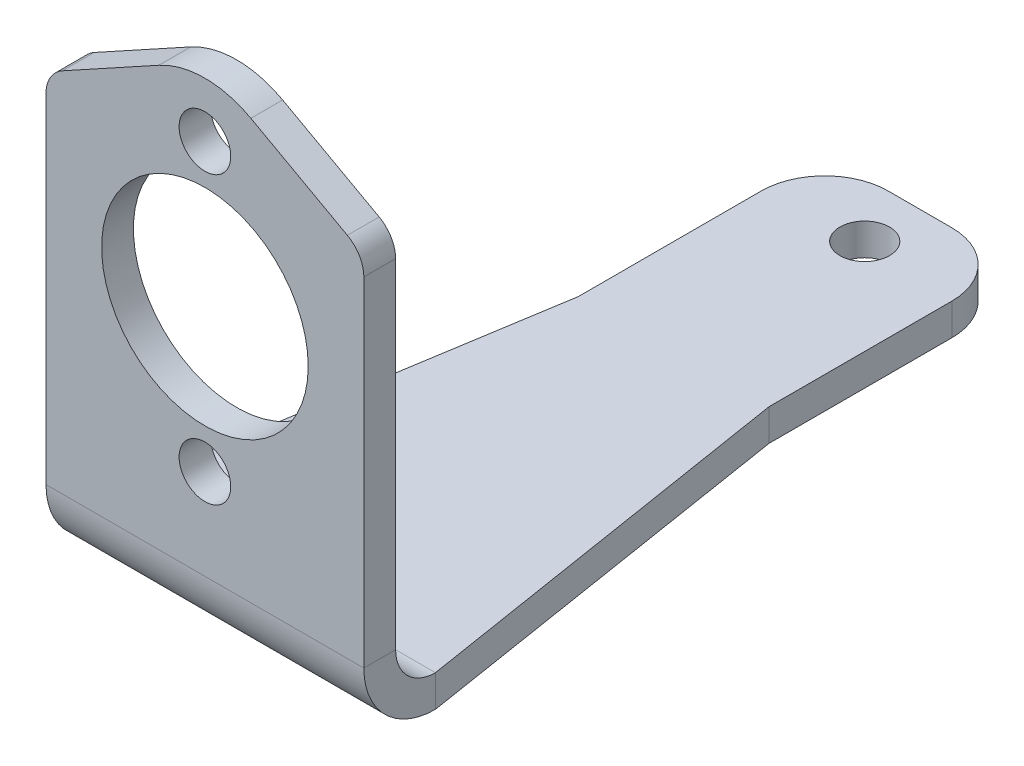
SolidWorks part; units mm, degrees
note: The reader was unsure of these and kept them because the rebuilt part matched: flange length of "Edge-Flange1".
material "Plain Carbon Steel"
ref_plane "Front" through (0, 0, 0) normal (0, 0, 1) x (1, 0, 0)
ref_plane "Top" through (0, 0, 0) normal (0, 1, 0) x (1, 0, 0)
ref_plane "Right" through (0, 0, 0) normal (1, 0, 0) x (0, 0, -1)
sketch "Sketch1" plane through (0, 0, 0) normal (0, 0, 1) x (1, 0, 0)
  line L0 (0, 85.725) -> (31.75, 103.1875)
  line L1 (0, 0) -> (63.5, 0)
  line L2 (0, 0) -> (0, 85.725)
  line L4 (63.5, 0) -> (63.5, 85.725)
  line L5 (31.75, 103.1875) -> (63.5, 85.725)
  circle A0 centre (31.75, 60.96) radius 20.6375
  circle A1 centre (31.75, 89.535) radius 5.1594
  circle A2 centre (31.75, 32.385) radius 5.1594
  point P7 (31.75, 0)
  dimension "D3" = 10.3187
  dimension "D4" = 41.275
  dimension "D1" = 63.5
  dimension "D2" = 32.385
  dimension "D5" = 28.575
  dimension "D6" = 28.575
  dimension "D7" = 103.1875
  dimension "D8" = 85.725
base flange "Base-Flange1" sketch "Sketch1" thickness 6.35 reverse thickness direction no parameters "D1"=7.9502
edge flange "Edge-Flange1" sketch "Sketch8" flange angle 90 flange length 142.875 flange position material inside bend radius 7.9502 thickness 6.35 relief rectangular parameters "D6"=10
sketch "Sketch8" plane through (0, 0, -6.35) normal (0, -1, 0) x (-1, 0, 0)
  line L2 (-63.5, 0) -> (-63.5, 136.525)
  line L3 (-63.5, 136.525) -> (0, 136.525)
  line L4 (0, 136.525) -> (0, 0)
  line L7 (0, 0) -> (-63.5, 0) construction
  line L8 (0, 0) -> (-63.5, 0)
  dimension "D1" = 136.525
bend "EdgeBend1" bend radius 7.9502 bend angle 90 parameters "D5"=1
sketch "Sketch9" plane through (0, 6.35, 0) normal (0, 1, 0) x (1, 0, 0)
  line L0 (0, 142.875) -> (63.5, 142.875) construction
  line L1 (63.5, 0) -> (31.75, 0) construction
  circle A0 centre (31.75, 30.226) radius 4.9609
  circle A1 centre (31.75, 131.826) radius 4.9609
  point P8 (31.75, 142.875)
  dimension "D1" = 9.9219
  dimension "D2" = 101.6
  dimension "D3" = 30.226
extrude "Cut-Extrude1" cut sketch "Sketch9" against normal through all normal cut yes
sketch "Sketch10" plane through (0, 0, 0) normal (0, -1, 0) x (1, 0, 0)
  line L0 (63.5, -142.875) -> (63.5, -14.3002) construction
  line L1 (0, -142.875) -> (12.7, -142.875)
  line L2 (0, -142.875) -> (0, -14.3002)
  line L4 (63.5, -142.875) -> (63.5, -14.3002)
  line L5 (0, -14.3002) -> (12.7, -93.6752)
  line L6 (12.7, -93.6752) -> (12.7, -142.875)
  line L7 (0, -14.3002) -> (63.5, -14.3002) construction
  line L8 (50.8, -142.875) -> (50.8, -93.6752)
  line L9 (50.8, -93.6752) -> (63.5, -14.3002)
  line L11 (50.8, -142.875) -> (63.5, -142.875)
  dimension "D1" = 12.7
  dimension "D2" = 38.1
  dimension "D3" = 79.375
extrude "Cut-Extrude2" cut sketch "Sketch10" against normal through all normal cut yes
fillet "Fillet1" radius 19.05 1 edges at (31.75, 103.1875, -3.175)
fillet "Fillet2" radius 6.35 2 edges at (63.5, 85.725, -3.175) (0, 85.725, -3.175)
fillet "Fillet3" radius 12.7 2 edges at (12.7, 3.175, -142.875) (50.8, 3.175, -142.875)
sketch "Bend-Lines1" [suppressed] plane through (0, 0, 0) normal (0, 1, 0) x (1, 0, 0)
sketch "Bounding-Box1" [suppressed] plane through (0, 0, 0) normal (0, 1, 0) x (1, 0, 0)
sheet metal parameters "Sheet-Metal28" thickness 6.35 parameters "D1"=7.9502
flat pattern "Flat-Pattern28" [suppressed]
sketch "Bend-Lines2" plane through (0, 0, 0) normal (0, 1, 0) x (1, 0, 0)
sketch3d "Bounding-Box2" [suppressed]
  line L0 (63.5, 103.1875, 0) -> (63.5, 0, 0) construction
  line L1 (0, 103.1875, 0) -> (0, 0, 0) construction
  line L2 (63.5, 103.1875, 0) -> (0, 103.1875, 0) construction
  line L3 (63.5, 0, 0) -> (0, 0, 0) construction
sheet metal parameters "Sheet-Metal29" thickness 6.35 parameters "D1"=7.9502
flat pattern "Flat-Pattern28"
sketch "Bend-Lines2" plane through (0, 0, 0) normal (0, 0, 1) x (1, 0, 0)
  line L0 (0, -8.7377) -> (63.5, -8.7377) construction
  line L1 (0, -8.7377) -> (63.5, -8.7377) construction
sketch3d "Bounding-Box2" [suppressed]
  line L0 (63.5, 103.1875, 0) -> (63.5, -138.3032, 0) construction
  line L1 (0, 103.1875, 0) -> (0, -138.3032, 0) construction
  line L2 (63.5, 103.1875, 0) -> (0, 103.1875, 0) construction
  line L3 (63.5, -138.3032, 0) -> (0, -138.3032, 0) construction
bend of the flat pattern "Flatten-<EdgeBend1>1"
sheet metal parameters "Sheet-Metal30" thickness 6.35 parameters "D1"=7.9502
flat pattern "Flat-Pattern28"
sketch "Bend-Lines2" plane through (0, 0, 0) normal (0, 0, 1) x (1, 0, 0)
  line L0 (0, -8.7377) -> (63.5, -8.7377) construction
  line L1 (0, -8.7377) -> (63.5, -8.7377) construction
sketch3d "Bounding-Box2" [suppressed]
  line L0 (63.5, 103.1875, 0) -> (63.5, -146.0502, 0) construction
  line L1 (0, 103.1875, 0) -> (0, -146.0502, 0) construction
  line L2 (63.5, 103.1875, 0) -> (0, 103.1875, 0) construction
  line L3 (63.5, -146.0502, 0) -> (0, -146.0502, 0) construction
bend of the flat pattern "Flatten-<EdgeBend1>1"
sheet metal parameters "Sheet-Metal31" thickness 6.35 parameters "D1"=7.9502
flat pattern "Flat-Pattern28"
sketch "Bend-Lines2" plane through (0, 0, 0) normal (0, 0, 1) x (1, 0, 0)
  line L0 (0, 5.5625) -> (63.5, 5.5625) construction
  line L1 (0, 5.5625) -> (63.5, 5.5625) construction
sketch3d "Bounding-Box2" [suppressed]
  line L0 (63.5, 100.4963, 0) -> (63.5, -131.75, 0) construction
  line L1 (0, 100.4963, 0) -> (0, -131.75, 0) construction
  line L2 (63.5, 100.4963, 0) -> (0, 100.4963, 0) construction
  line L3 (63.5, -131.75, 0) -> (0, -131.75, 0) construction
bend of the flat pattern "Flatten-<EdgeBend1>1"
equation "\"Total Cutting Length\"= \"Cutting Length-Outer\" + \"Cutting Length-Inner\""
equation "\"Amount in ft^2\"= \"Bounding Box Area-Blank\" / 144"
